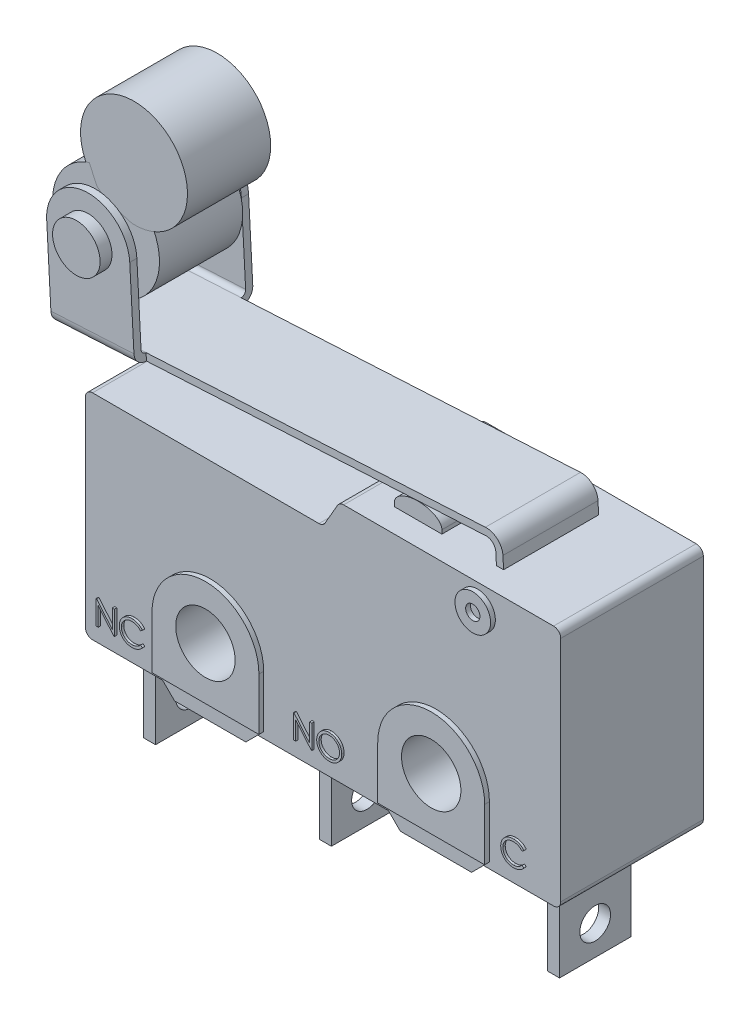
SolidWorks part; units mm, degrees
ref_plane "Plan de face" through (0, 0, 0) normal (0, 0, 1) x (1, 0, 0)
ref_plane "Plan de dessus" through (0, 0, 0) normal (0, 1, 0) x (1, 0, 0)
ref_plane "Plan de droite" through (0, 0, 0) normal (1, 0, 0) x (0, 0, -1)
sketch "Esquisse1" plane through (0, 0, 0) normal (0, 0, 1) x (1, 0, 0)
  line L0 (-6.5, 0) -> (-9.5, 0)
  line L1 (-9.5, 0) -> (-10, 0.5)
  line L2 (-10, 0.5) -> (-12.95, 0.5)
  line L3 (-13.25, 0.8) -> (-13.25, 9.2)
  line L4 (-12.95, 9.5) -> (-3.4232, 9.5)
  line L5 (-3.1634, 9.65) -> (-2.6438, 10.55)
  line L6 (-2.384, 10.7) -> (6.45, 10.7)
  line L7 (6.75, 10.4) -> (6.75, 0.8)
  line L8 (6.45, 0.5) -> (3.5, 0.5)
  line L9 (3.5, 0.5) -> (3, 0)
  line L10 (3, 0) -> (0, 0)
  line L11 (0, 0) -> (-0.5, 0.5)
  line L12 (-0.5, 0.5) -> (-6, 0.5)
  line L13 (-6, 0.5) -> (-6.5, 0)
  line L14 (-8, 2.95) -> (-8, 0) construction
  line L15 (1.5, 2.95) -> (1.5, 0) construction
  circle A0 centre (-8, 2.95) radius 1.25
  circle A1 centre (1.5, 2.95) radius 1.25
  arc A2 (-3.4232, 9.5) -> (-3.1634, 9.65) centre (-3.4232, 9.8) ccw
  arc A3 (-2.6438, 10.55) -> (-2.384, 10.7) centre (-2.384, 10.4) cw
  arc A4 (-12.95, 0.5) -> (-13.25, 0.8) centre (-12.95, 0.8) cw
  arc A5 (-13.25, 9.2) -> (-12.95, 9.5) centre (-12.95, 9.2) cw
  arc A6 (6.75, 0.8) -> (6.45, 0.5) centre (6.45, 0.8) cw
  arc A7 (6.45, 10.7) -> (6.75, 10.4) centre (6.45, 10.4) cw
  point P23 (-3.25, 9.5)
  point P30 (-13.25, 9.5)
  dimension "D2" = 9.5
  dimension "D3" = 2.5
  dimension "D4" = 2.95
  dimension "D11" = 0.3
  dimension "D1" = 3
  dimension "D5" = 5.25
  dimension "D6" = 20
  dimension "D7" = 10
  dimension "D8" = 1.2
  dimension "D9" = 10.7
  dimension "D10" = 0.5
  dimension "D12" = 120
  dimension "D13" = 135
extrude "Boss.-Extru.1" add sketch "Esquisse1" along normal mid plane 6
sketch "Esquisse2" plane through (0, 0, 0) normal (0, 0, 1) x (1, 0, 0)
  line L0 (-10.25, 0.75) -> (-5.75, 0.75)
  line L1 (-5.75, 0.75) -> (-5.75, 2.95)
  line L2 (-10.25, 2.95) -> (-10.25, 0.75)
  line L3 (-0.75, 2.95) -> (-0.75, 0.75)
  line L4 (-0.75, 0.75) -> (3.75, 0.75)
  line L5 (3.75, 0.75) -> (3.75, 2.95)
  line L6 (6.75, 0.8) -> (6.75, 10.4) construction
  line L7 (6.45, 10.7) -> (-2.384, 10.7) construction
  arc A0 (-5.75, 2.95) -> (-10.25, 2.95) centre (-8, 2.95) ccw
  circle A1 centre (-8, 2.95) radius 1.25 construction
  circle A2 centre (-8, 2.95) radius 1.25
  arc A3 (3.75, 2.95) -> (-0.75, 2.95) centre (1.5, 2.95) ccw
  circle A4 centre (1.5, 2.95) radius 1.25
  circle A5 centre (3.25, 9.7) radius 0.75
  circle A6 centre (3.25, 9.7) radius 0.3
  dimension "D1" = 2.25
  dimension "D5" = 3.5
  dimension "D7" = 1.5
  dimension "D8" = 0.6
  dimension "D2" = 2.2
  dimension "D4" = 5
  dimension "D6" = 1
  dimension "D3" = 2
extrude "Boss.-Extru.2" add sketch "Esquisse2" along normal mid plane 6.4
sketch "Esquisse3" plane through (0, 0, -3) normal (0, 0, -1) x (-1, 0, 0)
  text T0 "5A 125-250V~ 10T85" font "Century Gothic" height 1
extrude "Boss.-Extru.3" add sketch "Esquisse3" along normal blind 0.1
sketch "Esquisse5" plane through (0, 0, 0) normal (0, 0, 1) x (1, 0, 0)
  line L0 (-1.25, 10.8586) -> (-1.25, 10.7)
  line L1 (6.45, 10.7) -> (-2.384, 10.7) construction
  line L2 (-1.25, 10.7) -> (0.75, 10.7)
  line L3 (0.75, 10.7) -> (0.75, 10.8586)
  line L4 (6.75, 0.8) -> (6.75, 10.4) construction
  ellipse E0 centre (-0.25, 10.8586) end of major axis (-1.25, 10.8586) minor radius 0.5414 (0.75, 10.8586) -> (-1.25, 10.8586) ccw
  dimension "D1" = 2
  dimension "D2" = 6
  dimension "D3" = 0.7
extrude "Boss.-Extru.4" add sketch "Esquisse5" along normal mid plane 4
sketch "Esquisse7" plane through (0, 0, -3) normal (0, 0, -1) x (-1, 0, 0)
  text T0 "1                 3                  2" font "Century Gothic" height 1
extrude "Boss.-Extru.5" add sketch "Esquisse7" along normal blind 0.1
sketch "Esquisse8" plane through (0, 0, 3) normal (0, 0, 1) x (1, 0, 0)
  text T0 "NC                NO                 C" font "Century Gothic" height 1
extrude "Boss.-Extru.6" add sketch "Esquisse8" along normal blind 0.1
sketch "Esquisse9" plane through (0, 0, 0) normal (0, 0, 1) x (1, 0, 0)
  line L0 (3.0454, 10.7) -> (3.0188, 11.1897)
  line L1 (6.45, 10.7) -> (-2.384, 10.7) construction
  line L2 (2.5977, 11.5674) -> (-15.1761, 10.6017)
  line L3 (-15.1761, 10.6017) -> (-15.1923, 10.9012)
  line L5 (-15.1923, 10.9012) -> (2.5815, 11.8669)
  line L6 (3.3184, 11.2059) -> (3.3459, 10.7)
  line L7 (3.3459, 10.7) -> (3.0454, 10.7)
  line L8 (3.25, 9.7) -> (3.1957, 10.7) construction
  arc A1 (3.0188, 11.1897) -> (2.5977, 11.5674) centre (2.6194, 11.168) ccw
  arc A2 (2.5815, 11.8669) -> (3.3184, 11.2059) centre (2.6194, 11.168) cw
  spline S0 degree 3 poles (-2241.0488, 2001.2399) (-95.2248, -57.966) (7.577, 7.3982) (0.2748, 11.3515) (0.0132, 11.41) (-0.5132, 11.41) (-0.7748, 11.3515) (-8.077, 7.3982) (94.7243, -57.9657) (2240.532, 2001.2239) knots -9.259767 -9.259767 -9.259767 -9.259767 0.25 0.25 0.5 0.5 0.75 0.75 10.259743 10.259743 10.259743 10.259743 only from (0.76, 10.8586) to (-1.26, 10.8586)
  spline S1 degree 3 poles (0.76, 10.8586) (0.76, 11.0052) (0.6489, 11.149) (0.2748, 11.3515) (0.0132, 11.41) (-0.5132, 11.41) (-0.7748, 11.3515) (-1.1489, 11.149) (-1.26, 11.0052) (-1.26, 10.8586) knots 0 0 0 0 0.25 0.25 0.5 0.5 0.75 0.75 1 1 1 1 construction
  dimension "D4" = 0.4
  dimension "D5" = 0.7
  dimension "D1" = 0.3
  dimension "D2" = 0.3
  dimension "D3" = 2.2
  dimension "D6" = 18.5
  dimension "D7" = 0.01
extrude "Boss.-Extru.15" add sketch "Esquisse9" along normal mid plane 4
sketch "Esquisse10" plane through (0, 0, 0) normal (0, 0, 1) x (1, 0, 0)
  line L0 (-15.1761, 10.6017) -> (-15.3795, 14.3462)
  line L1 (-11.8847, 14.536) -> (-11.6812, 10.7916)
  line L2 (-15.1761, 10.6017) -> (2.5977, 11.5674) construction
  line L3 (-11.6812, 10.7916) -> (-15.1761, 10.6017)
  arc A0 (-15.3795, 14.3462) -> (-11.8847, 14.536) centre (-13.6321, 14.4411) cw
  dimension "D1" = 3.5
  dimension "D2" = 3.75
extrude "Boss.-Extru.16" add sketch "Esquisse10" along normal mid plane 5
sketch "Esquisse11" plane through (0, 0, 0) normal (0, 0, 1) x (1, 0, 0)
  line L0 (-11.6975, 11.0911) -> (-15.1923, 10.9012)
  line L1 (-15.3795, 14.3462) -> (-15.1761, 10.6017) construction
  line L2 (-15.1923, 10.9012) -> (-15.5026, 16.6115)
  line L3 (-15.5026, 16.6115) -> (-12.0077, 16.8014)
  line L4 (-12.0077, 16.8014) -> (-11.6975, 11.0911)
extrude "Enlèv. mat.-Extru.1" cut sketch "Esquisse11" against normal mid plane 4.4
sketch "Esquisse12" plane through (0, 0, 0) normal (0, 0, 1) x (1, 0, 0)
  circle A0 centre (-13.6321, 14.4411) radius 1
  dimension "D1" = 2
extrude "Boss.-Extru.17" add sketch "Esquisse12" along normal mid plane 6
sketch "Esquisse13" plane through (0, 0, 0) normal (0, 0, 1) x (1, 0, 0)
  circle A0 centre (-13.6321, 14.4411) radius 2.25
  dimension "D1" = 4.5
extrude "Boss.-Extru.18" add sketch "Esquisse13" along normal mid plane 3.5
fillet "Congé1" radius 0.2 2 edges at (-13.4449, 10.9962, 2.2) (-13.4449, 10.9962, -2.2)
fillet "Congé2" radius 0.5 2 edges at (-13.4286, 10.6966, 2.5) (-13.4286, 10.6966, -2.5)
sketch "Esquisse15" plane through (0, 0, 0) normal (0, 0, 1) x (1, 0, 0)
  line L1 (4.7, 0.5) -> (5.2, 0.5)
  line L2 (4.7, 0.5) -> (4.7, -3.5)
  line L3 (4.7, -3.5) -> (5.2, -3.5)
  line L4 (5.2, 0.5) -> (5.2, -3.5)
  line L5 (-6, 0.5) -> (-0.5, 0.5) construction
  line L6 (-4.9, 0.5) -> (-4.4, 0.5)
  line L7 (-4.9, 0.5) -> (-4.9, -3.5)
  line L8 (-4.9, -3.5) -> (-4.4, -3.5)
  line L9 (-4.4, 0.5) -> (-4.4, -3.5)
  line L10 (-12.95, 0.5) -> (-10, 0.5) construction
  line L11 (-12.3, 0.5) -> (-11.8, 0.5)
  line L12 (-12.3, 0.5) -> (-12.3, -3.5)
  line L13 (-12.3, -3.5) -> (-11.8, -3.5)
  line L14 (-11.8, 0.5) -> (-11.8, -3.5)
  line L16 (6.75, 0.8) -> (6.75, 10.4) construction
  dimension "D1" = 9.6
  dimension "D2" = 7.4
  dimension "D3" = 0.5
  dimension "D4" = 1.55
  dimension "D5" = 4
extrude "Boss.-Extru.19" add sketch "Esquisse15" along normal mid plane 3 separate body
sketch "Esquisse16" plane through (-12.3, 0, 0) normal (-1, 0, 0) x (0, 0, 1)
  circle A0 centre (0, -2.2572) radius 0.647
extrude "Enlèv. mat.-Extru.2" cut sketch "Esquisse16" against normal through all
sketch "Esquisse17" plane through (0, 0, 0) normal (0, 0, 1) x (1, 0, 0)
  line L0 (-3.4232, 9.5) -> (-12.95, 9.5) construction
  arc A0 (-13.6321, 14.4411) -> (-12.4549, 17.5) centre (3.25, 9.7) cw construction
  circle A1 centre (-12.4549, 17.5) radius 2.25
  dimension "D1" = 8
extrude "Boss.-Extru.20" add sketch "Esquisse17" along normal mid plane 3.5 separate body
